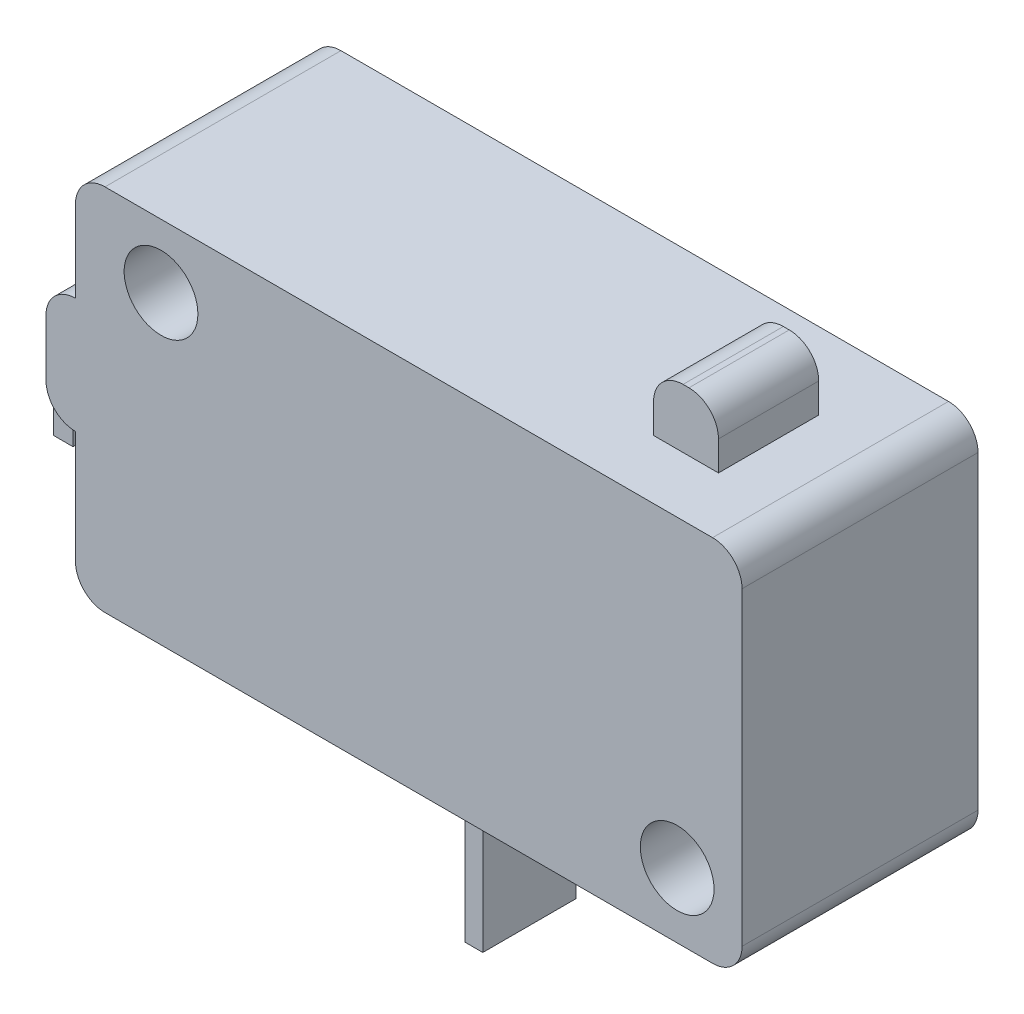
SolidWorks part; units mm, degrees
ref_plane "Front Plane" through (0, 0, 0) normal (0, 0, 1) x (1, 0, 0)
ref_plane "Top Plane" through (0, 0, 0) normal (0, 1, 0) x (1, 0, 0)
ref_plane "Right Plane" through (0, 0, 0) normal (1, 0, 0) x (0, 0, -1)
sketch "Sketch1" plane through (0, 0, 0) normal (0, 0, 1) x (1, 0, 0)
  line L1 (0, 0) -> (28.702, 0)
  line L2 (0, 0) -> (0, 15.875)
  line L3 (0, 15.875) -> (28.702, 15.875)
  line L4 (28.702, 0) -> (28.702, 15.875)
  dimension "D1" = 15.875
  dimension "D2" = 28.702
extrude "Boss-Extrude1" add sketch "Sketch1" along normal blind 10.16
sketch "Sketch2" plane through (0, 0, 10.16) normal (0, 0, 1) x (1, 0, 0)
  line L1 (28.702, 0) -> (28.702, 15.875) construction
  line L3 (0, 0) -> (28.702, 0) construction
  circle A0 centre (3.683, 13.1318) radius 1.5875
  circle A1 centre (25.908, 2.794) radius 1.5875
  dimension "D1" = 22.225
  dimension "D2" = 3.175
  dimension "D3" = 3.175
  dimension "D4" = 2.794
  dimension "D5" = 10.3378
  dimension "D6" = 2.794
extrude "Cut-Extrude1" cut sketch "Sketch2" against normal blind 12.4206
sketch "Sketch4" plane through (0, 0, 0) normal (0, -1, 0) x (-1, 0, 0)
  line L1 (-14.9668, -4.3293) -> (-15.7305, -4.3293)
  line L2 (-14.9668, -4.3293) -> (-14.9668, -8.3512)
  line L3 (-14.9668, -8.3512) -> (-15.7305, -8.3512)
  line L4 (-15.7305, -4.3293) -> (-15.7305, -8.3512)
extrude "Boss-Extrude2" add sketch "Sketch4" along normal blind 6.35
sketch "Sketch5" plane through (0, 0, 0) normal (-1, 0, 0) x (0, 0, 1)
  line L1 (3.9336, 7.3067) -> (8.0513, 7.3067)
  line L2 (3.9336, 7.3067) -> (3.9336, 6.4361)
  line L3 (3.9336, 6.4361) -> (8.0513, 6.4361)
  line L4 (8.0513, 7.3067) -> (8.0513, 6.4361)
extrude "Boss-Extrude3" add sketch "Sketch5" along normal blind 3.048
sketch "Sketch6" plane through (0, 6.4361, 0) normal (0, -1, 0) x (-1, 0, 0)
  line L0 (3.048, -8.0513) -> (0, -8.0513) construction
  line L1 (3.048, -3.9336) -> (2.2147, -3.9336)
  line L2 (3.048, -3.9336) -> (3.048, -8.0513)
  line L3 (3.048, -8.0513) -> (2.2147, -8.0513)
  line L4 (2.2147, -3.9336) -> (2.2147, -8.0513)
extrude "Boss-Extrude4" add sketch "Sketch6" along normal blind 3.048
fillet "Fillet1" radius 0.508 1 edges at (-3.048, 7.3067, 5.9924)
sketch "Sketch7" plane through (0, 0, 0) normal (-1, 0, 0) x (0, 0, 1)
  line L0 (0, 15.875) -> (0, 0) construction
  line L1 (0, 6.1203) -> (10.16, 6.1203)
  line L2 (0, 6.1203) -> (0, 11.0867)
  line L3 (0, 11.0867) -> (10.16, 11.0867)
  line L4 (10.16, 6.1203) -> (10.16, 11.0867)
  line L5 (10.16, 15.875) -> (10.16, 0) construction
extrude "Boss-Extrude5" add sketch "Sketch7" along normal blind 1.27
sketch "Sketch8" plane through (0, 15.875, 0) normal (0, 1, 0) x (1, 0, 0)
  line L0 (28.702, -10.16) -> (28.702, 0) construction
  line L1 (22.352, -3.302) -> (25.146, -3.302)
  line L2 (22.352, -3.302) -> (22.352, -7.62)
  line L3 (22.352, -7.62) -> (25.146, -7.62)
  line L4 (25.146, -3.302) -> (25.146, -7.62)
  line L5 (28.702, -10.16) -> (0, -10.16) construction
  dimension "D1" = 2.794
  dimension "D2" = 4.318
  dimension "D3" = 3.556
  dimension "D4" = 2.54
extrude "Boss-Extrude6" add sketch "Sketch8" along normal blind 2.54
fillet "Fillet3" radius 1.27 2 edges at (25.146, 18.415, 5.461) (22.352, 18.415, 5.461)
fillet "Fillet5" radius 1.27 4 edges at (28.702, 0, 5.08) (0, 0, 5.08) (28.702, 15.875, 5.08) (0, 15.875, 5.08)
fillet "Fillet6" radius 1.27 2 edges at (-1.27, 6.1203, 5.08) (-1.27, 11.0867, 5.08)
